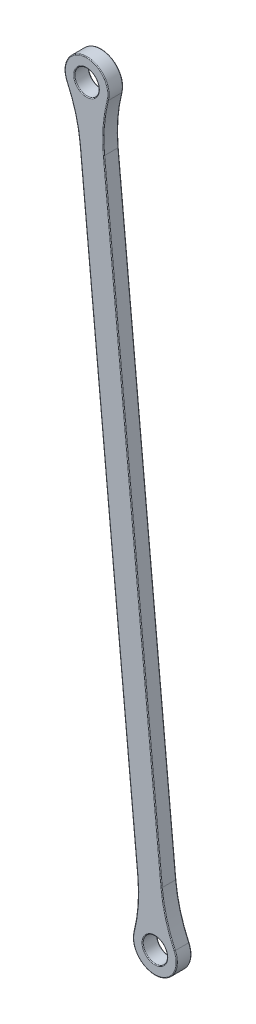
SolidWorks part; units mm, degrees
ref_plane "Front Plane" through (0, 0, 0) normal (0, 0, 1) x (1, 0, 0)
ref_plane "Top Plane" through (0, 0, 0) normal (0, 1, 0) x (1, 0, 0)
ref_plane "Right Plane" through (0, 0, 0) normal (1, 0, 0) x (0, 0, -1)
sketch "Sketch1" plane through (0, 0, 0) normal (0, 0, 1) x (1, 0, 0)
  line L0 (14.5, 81.5) -> (0.465, 228.833) construction
  line L1 (14.5, 81.5) -> (0.465, 228.833) construction
sketch "Sketch2" plane through (0, 0, 0) normal (0, 0, 1) x (1, 0, 0)
  line L0 (14.5, 81.5) -> (0.465, 228.833) construction
  line L1 (14.5, 81.5) -> (0.465, 228.833) construction
  line L2 (12.0113, 81.2629) -> (-2.0237, 228.5959)
  line L3 (16.9887, 81.7371) -> (2.9538, 229.0701)
  circle A0 centre (0.465, 228.833) radius 4.5 construction
  circle A1 centre (14.5, 81.5) radius 4.5 construction
  arc A2 (12.0113, 81.2629) -> (16.9887, 81.7371) centre (14.5, 81.5) ccw
  arc A3 (2.9538, 229.0701) -> (-2.0237, 228.5959) centre (0.465, 228.833) ccw
  arc A4 (2.9538, 229.0701) -> (-2.0237, 228.5959) centre (0.465, 228.833) cw
  arc A5 (16.9887, 81.7371) -> (12.0113, 81.2629) centre (14.5, 81.5) ccw
  arc A6 (3.3086, 225.3453) -> (-1.6689, 224.8712) centre (0.465, 228.833) ccw
  arc A7 (16.6339, 85.4619) -> (11.6564, 84.9877) centre (14.5, 81.5) cw
  point P7 (7.4825, 155.1665)
  dimension "D1" = 9
  dimension "D2" = 9
  dimension "D3" = 5
extrude "Boss-Extrude2" add sketch "Sketch2" against normal blind 3 contours A7 L3 A2 L2 | A5 L3 A4 L2 | L3 A6 L2 A3 region at (14.7488, 78.8883, 0) region at (7.4825, 155.1665, 0) region at (0.05, 233.1898, 0)
fillet "Fillet1" radius 30 4 edges at (16.6339, 85.4619, -1.5) (3.3086, 225.3453, -1.5) (-1.6689, 224.8712, -1.5) (11.6564, 84.9877, -1.5)
fillet "Fillet2" radius 0.15 20 edges at (17, 81.5, -3) (4.0032, 222.6725, -3) (0.0383, 233.3127, -3) (-1.8463, 222.1153, -3) (4.9938, 154.9294, -3) (10.9619, 87.6605, -3) (14.9267, 77.0203, -3) (16.8113, 88.2178, -3) (9.9712, 155.4036, -3) (2.965, 228.833, -3) (17, 81.5, 0) (10.9619, 87.6605, 0) (4.9938, 154.9294, 0) (-1.8463, 222.1153, 0) (0.0383, 233.3127, 0) (4.0032, 222.6725, 0) (9.9712, 155.4036, 0) (16.8113, 88.2178, 0) (14.9267, 77.0203, 0) (2.965, 228.833, 0)
